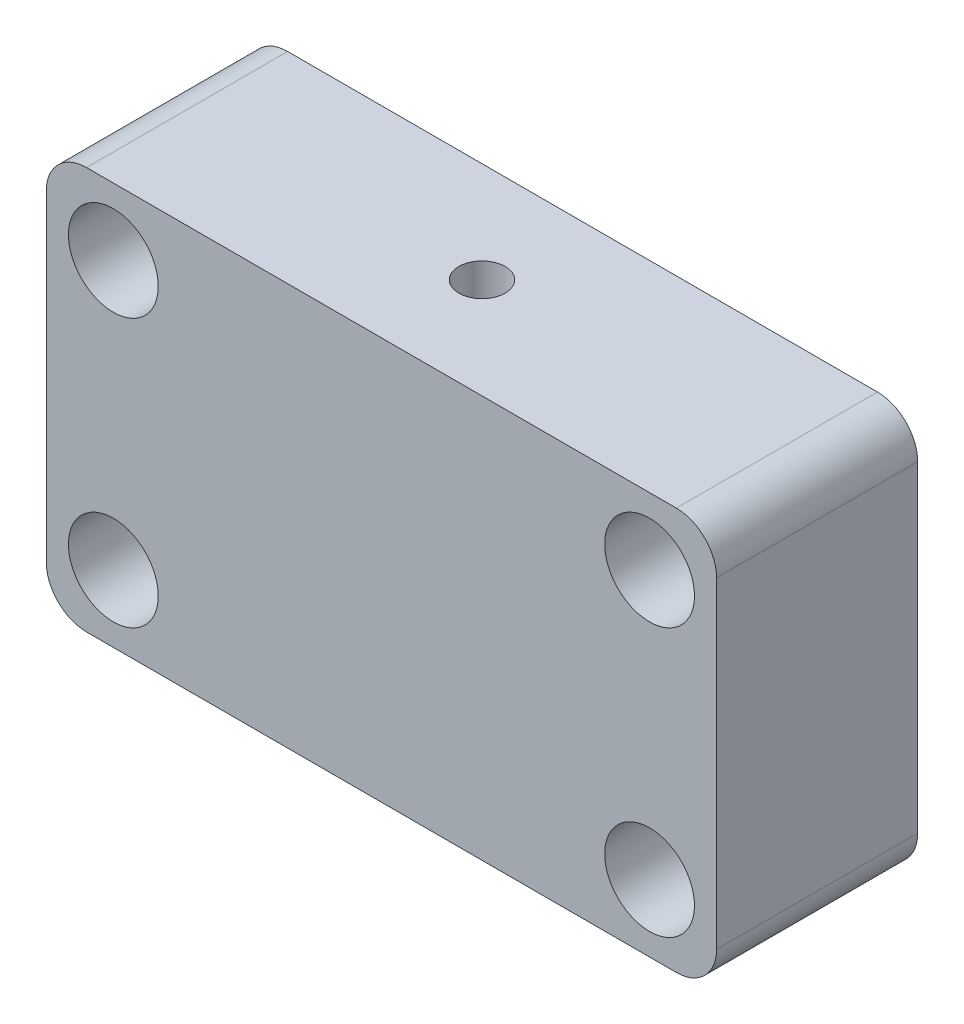
SolidWorks part; units mm, degrees
ref_plane "Front Plane" through (0, 0, 0) normal (0, 0, 1) x (1, 0, 0)
ref_plane "Top Plane" through (0, 0, 0) normal (0, 1, 0) x (1, 0, 0)
ref_plane "Right Plane" through (0, 0, 0) normal (1, 0, 0) x (0, 0, -1)
sketch "Sketch2" plane through (0, 0, 0) normal (0, 0, 1) x (1, 0, 0)
  line L1 (-25, -15) -> (25, -15)
  line L2 (-25, -15) -> (-25, 15)
  line L3 (-25, 15) -> (25, 15)
  line L4 (25, -15) -> (25, 15)
  line L5 (-25, -15) -> (25, 15) construction
  line L6 (-25, 15) -> (25, -15) construction
  circle A0 centre (20, 10) radius 3.35
  circle A1 centre (-20, 10) radius 3.35
  circle A2 centre (-20, -10) radius 3.35
  circle A3 centre (20, -10) radius 3.35
  point P0 (0, 0)
  dimension "D3" = 20
  dimension "D1" = 30
  dimension "D2" = 50
  dimension "D4" = 10
extrude "Boss-Extrude1" add sketch "Sketch2" along normal blind 15
sketch "Sketch7" plane through (0, 15, 0) normal (0, 1, 0) x (1, 0, 0)
  line L0 (0, 0) -> (0, -15) construction
  line L1 (25, 0) -> (-25, 0) construction
  line L2 (25, -15) -> (-25, -15) construction
  point P6 (0, -7.5)
sketch "Sketch8" plane through (0, 0, 0) normal (0, 0, -1) x (-1, 0, 0)
  line L0 (25, -15) -> (-25, 15) construction
  line L1 (25, 15) -> (-25, -15) construction
  point P4 (0, 0)
hole_wizard "#8-32 Tapped Hole1" positions "3DSketch1" profile "Sketch9" tap size "#8-32" standard "ANSI Inch"
sketch3d "3DSketch1"
  point P0 (0, 15, 7.5)
sketch "Sketch9" plane through (0, 15, 7.5) normal (1, 0, 0) x (0, 0, 1)
  line L0 (0, 0) -> (0, 6.0378)
  line L1 (0, 6.0378) -> (1.7272, 5)
  line L2 (1.7272, 5) -> (1.7272, 0)
  line L5 (1.7272, 0) -> (0, 0)
  line L10 (0, 6.0378) -> (-1.7272, 5) construction
  line L11 (0, -6.35) -> (0, 107.95) construction
  dimension "Tap Drill Dia." = 3.4544
  dimension "Tap Drill Depth" = 5
  dimension "Drill Angle" = 118
fillet "Fillet1" radius 3 1 edges at (25, 15, 7.5)
fillet "Fillet2" radius 3 1 edges at (-25, 15, 7.5)
fillet "Fillet3" radius 3 1 edges at (25, -15, 7.5)
fillet "Fillet4" radius 3 1 edges at (-25, -15, 7.5)
